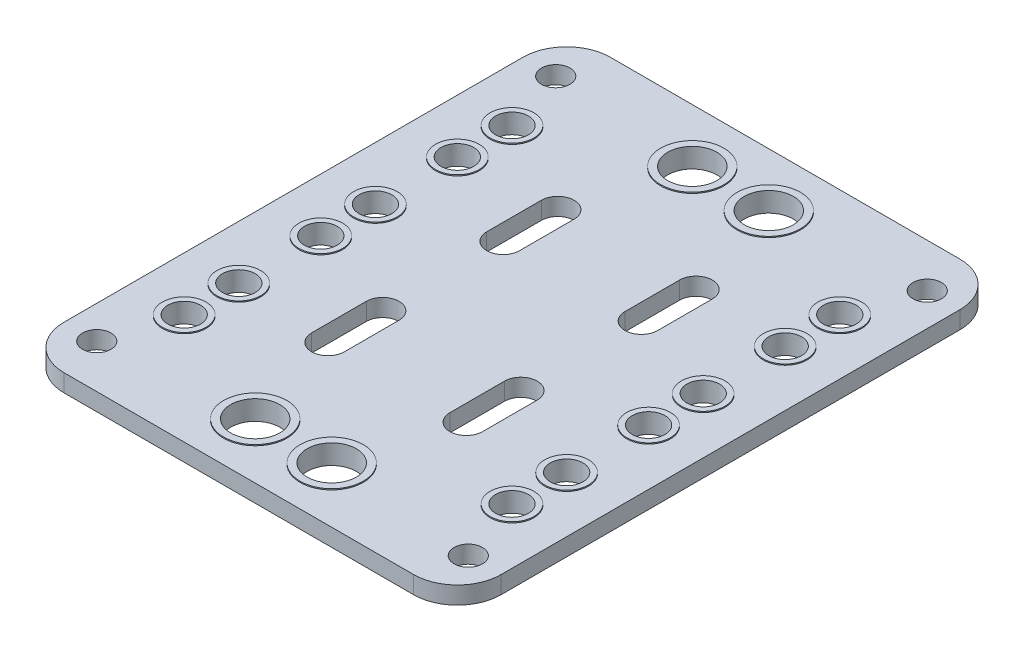
SolidWorks part; units mm, degrees
ref_plane "Alzado" through (0, 0, 0) normal (0, 0, 1) x (1, 0, 0)
ref_plane "Planta" through (0, 0, 0) normal (0, 1, 0) x (1, 0, 0)
ref_plane "Vista lateral" through (0, 0, 0) normal (1, 0, 0) x (0, 0, -1)
sketch "Croquis1" plane through (0, 0, 0) normal (0, 1, 0) x (1, 0, 0)
  line L1 (-16, 25) -> (16, 25)
  line L2 (-20, 21) -> (-20, -21)
  line L3 (-16, -25) -> (16, -25)
  line L4 (20, 21) -> (20, -21)
  line L5 (-20, 25) -> (20, -25) construction
  line L6 (-20, -25) -> (20, 25) construction
  arc A0 (16, 25) -> (20, 21) centre (16, 21) cw
  arc A1 (16, -25) -> (20, -21) centre (16, -21) ccw
  arc A2 (-20, -21) -> (-16, -25) centre (-16, -21) ccw
  arc A3 (-16, 25) -> (-20, 21) centre (-16, 21) ccw
  point P0 (0, 0)
  dimension "D1" = 4
  dimension "D2" = 50
  dimension "D3" = 40
extrude "Saliente-Extruir1" add sketch "Croquis1" along normal mid plane 1.6
sketch "Croquis2" plane through (0, 0.8, 0) normal (0, 1, 0) x (1, 0, 0)
  line L1 (17, -21) -> (-17, -21) construction
  line L2 (17, -21) -> (17, 21) construction
  line L3 (17, 21) -> (-17, 21) construction
  line L4 (-17, -21) -> (-17, 21) construction
  line L5 (17, -21) -> (-17, 21) construction
  line L6 (17, 21) -> (-17, -21) construction
  circle A0 centre (-17, 21) radius 1.3
  circle A1 centre (17, 21) radius 1.3
  circle A2 centre (17, -21) radius 1.3
  circle A3 centre (-17, -21) radius 1.3
  point P0 (0, 0)
  dimension "D1" = 2.6
  dimension "D2" = 42
  dimension "D3" = 34
extrude "Cortar-Extruir1" cut sketch "Croquis2" against normal through all both and the other way through all
sketch "Croquis6" plane through (0, 0.8, 0) normal (0, 1, 0) x (1, 0, 0)
  line L0 (-3.5, 20) -> (3.5, 20) construction
  line L1 (0, 23.1314) -> (0, -25.294) construction
  line L2 (-15, 15) -> (-15, 10) construction
  line L3 (-15, 2.5) -> (-15, -2.5) construction
  line L4 (-15, -10) -> (-15, -15) construction
  line L5 (-20, 21) -> (-20, -21) construction
  line L6 (16, 25) -> (-16, 25) construction
  line L7 (-16, -25) -> (16, -25) construction
  line L8 (-3.5, 0) -> (3.5, 0) construction
  line L9 (-3.5, -20) -> (3.5, -20) construction
  line L10 (-6.3249, 10.5125) -> (-6.3249, 5.5125) construction
  line L11 (-4.8249, 10.5125) -> (-4.8249, 5.5125)
  line L12 (-7.8249, 10.5125) -> (-7.8249, 5.5125)
  line L13 (6.3249, 10.5125) -> (6.3249, 5.5125) construction
  line L14 (4.8249, 10.5125) -> (4.8249, 5.5125)
  line L15 (7.8249, 10.5125) -> (7.8249, 5.5125)
  line L16 (-6.3249, -10.5125) -> (-6.3249, -5.5125) construction
  line L17 (-4.8249, -10.5125) -> (-4.8249, -5.5125)
  line L18 (-7.8249, -10.5125) -> (-7.8249, -5.5125)
  line L19 (6.3249, -10.5125) -> (6.3249, -5.5125) construction
  line L20 (4.8249, -10.5125) -> (4.8249, -5.5125)
  line L21 (7.8249, -10.5125) -> (7.8249, -5.5125)
  circle A0 centre (-3.5, 20) radius 2.25
  circle A1 centre (3.5, 20) radius 2.25
  circle A2 centre (-15, 2.5) radius 1.5
  circle A3 centre (-15, -2.5) radius 1.5
  circle A4 centre (-15, 10) radius 1.5
  circle A5 centre (-15, 15) radius 1.5
  circle A6 centre (-15, -10) radius 1.5
  circle A7 centre (-15, -15) radius 1.5
  circle A8 centre (15, -15) radius 1.5
  circle A9 centre (15, -10) radius 1.5
  circle A10 centre (15, 15) radius 1.5
  circle A11 centre (15, 10) radius 1.5
  circle A12 centre (15, -2.5) radius 1.5
  circle A13 centre (15, 2.5) radius 1.5
  circle A14 centre (3.5, -20) radius 2.25
  circle A15 centre (-3.5, -20) radius 2.25
  arc A16 (-4.8249, 10.5125) -> (-7.8249, 10.5125) centre (-6.3249, 10.5125) ccw
  arc A17 (-7.8249, 5.5125) -> (-4.8249, 5.5125) centre (-6.3249, 5.5125) ccw
  arc A18 (4.8249, 10.5125) -> (7.8249, 10.5125) centre (6.3249, 10.5125) cw
  arc A19 (7.8249, 5.5125) -> (4.8249, 5.5125) centre (6.3249, 5.5125) cw
  arc A20 (-4.8249, -10.5125) -> (-7.8249, -10.5125) centre (-6.3249, -10.5125) cw
  arc A21 (-7.8249, -5.5125) -> (-4.8249, -5.5125) centre (-6.3249, -5.5125) cw
  arc A22 (4.8249, -10.5125) -> (7.8249, -10.5125) centre (6.3249, -10.5125) ccw
  arc A23 (7.8249, -5.5125) -> (4.8249, -5.5125) centre (6.3249, -5.5125) ccw
  point P4 (0, 20)
  point P32 (-15, 0)
  point P46 (-6.3249, 8.0125)
  point P54 (6.3249, 8.0125)
  point P61 (-6.3249, -8.0125)
  point P68 (6.3249, -8.0125)
  point P73 (6.3249, 8.0125)
  dimension "D1" = 3
  dimension "D8" = 4.5
  dimension "D2" = 5
  dimension "D3" = 5
  dimension "D4" = 5
  dimension "D5" = 5
  dimension "D6" = 10
  dimension "D7" = 10
  dimension "D9" = 7
  dimension "D10" = 5
  dimension "D11" = 3
  dimension "D12" = 5
extrude "Cortar-Extruir3" cut sketch "Croquis6" against normal through all
sketch "Croquis7" plane through (0, 0, 0) normal (0, 1, 0) x (1, 0, 0)
  line L0 (0, 6.6749) -> (0, -3.6027) construction
  line L1 (-7.0195, 0) -> (8.7807, 0) construction
  circle A0 centre (-15, -15) radius 1.5
  circle A1 centre (-15, -10) radius 1.5
  circle A2 centre (-15, -2.5) radius 1.5
  circle A3 centre (-15, 2.5) radius 1.5
  circle A4 centre (-15, 10) radius 1.5
  circle A5 centre (-15, 15) radius 1.5
  circle A6 centre (-15, 15) radius 1.5 construction
  circle A7 centre (-15, 15) radius 2
  circle A8 centre (-15, 10) radius 2
  circle A9 centre (-15, 2.5) radius 2
  circle A10 centre (-15, -2.5) radius 2
  circle A11 centre (-15, -15) radius 2
  circle A12 centre (-15, -10) radius 2
  circle A13 centre (-3.5, 20) radius 2.25
  circle A14 centre (-3.5, 20) radius 2.8949
  circle A15 centre (3.5, 20) radius 2.8949
  circle A16 centre (3.5, 20) radius 2.25
  circle A17 centre (15, -10) radius 2
  circle A18 centre (15, -15) radius 2
  circle A19 centre (15, -2.5) radius 2
  circle A20 centre (15, 2.5) radius 2
  circle A21 centre (15, 10) radius 2
  circle A22 centre (15, 15) radius 2
  circle A23 centre (15, 15) radius 1.5
  circle A24 centre (15, 10) radius 1.5
  circle A25 centre (15, 2.5) radius 1.5
  circle A26 centre (15, -2.5) radius 1.5
  circle A27 centre (15, -10) radius 1.5
  circle A28 centre (15, -15) radius 1.5
  circle A29 centre (3.5, -20) radius 2.25
  circle A30 centre (3.5, -20) radius 2.8949
  circle A31 centre (-3.5, -20) radius 2.8949
  circle A32 centre (-3.5, -20) radius 2.25
  dimension "D1" = 4
extrude "Saliente-Extruir3" add sketch "Croquis7" along normal mid plane 1.8
